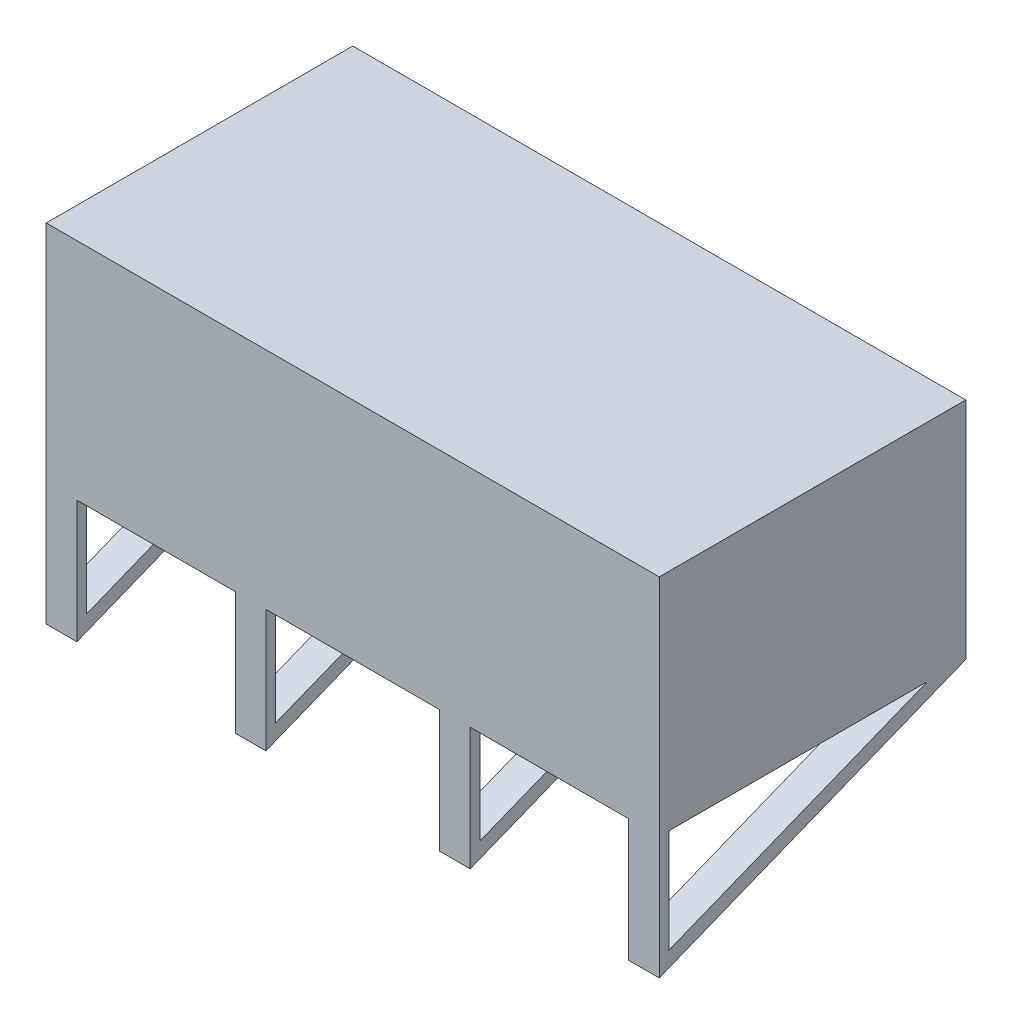
SolidWorks part; units mm, degrees
ref_plane "Front Plane" through (0, 0, 0) normal (0, 0, 1) x (1, 0, 0)
ref_plane "Top Plane" through (0, 0, 0) normal (0, 1, 0) x (1, 0, 0)
ref_plane "Right Plane" through (0, 0, 0) normal (1, 0, 0) x (0, 0, -1)
sketch "LeftSideSketch" plane through (0, 0, 0) normal (1, 0, 0) x (0, 0, -1)
  line L0 (0, 0) -> (150, 0)
  line L1 (150, 0) -> (150, -110)
  line L3 (0, -110) -> (0, 0)
  line L5 (5, -5) -> (5, -105)
  line L6 (5, -105) -> (145, -105)
  line L7 (145, -105) -> (145, -5)
  line L9 (5, -5) -> (145, -5)
  line L10 (0, -110) -> (0, -170)
  line L11 (0, -170) -> (150, -110)
  line L12 (4.8121, -110) -> (4.8121, -160.5359)
  line L13 (4.8121, -160.5359) -> (131.1519, -110)
  line L15 (0, -110) -> (4.8121, -110)
  line L16 (4.8121, -110) -> (131.1519, -110)
  line L17 (131.1519, -110) -> (150, -110)
  dimension "D1" = 150
  dimension "D2" = 110
  dimension "D3" = 5
  dimension "D4" = 5
  dimension "D5" = 5
  dimension "D6" = 5
  dimension "D7" = 7
  dimension "D8" = 4.8121
  dimension "D10" = 60
extrude "Boss-Extrude1" add sketch "LeftSideSketch" along normal blind 300 contours L3 L1 L0 L5 L9 L7 L6 region at (0, -1.8601, -75)
extrude "Boss-Extrude2" add sketch "LeftSideSketch<4>" along normal blind 15 contours L10 L11 L13 L12 region at (0, -111.6155, -2.406)
sketch "LeftSideSketch<4>" plane through (0, 0, 0) normal (1, 0, 0) x (0, 0, -1) same geometry as "LeftSideSketch"
extrude "Boss-Extrude3" add sketch "LeftSideSketch<5>" against normal blind 15 from surface contours L10 L11 L13 L12 region at (0, -111.6155, -2.406) starting at face at (300, -55, -75)
sketch "LeftSideSketch<5>" plane through (0, 0, 0) normal (1, 0, 0) x (0, 0, -1) same geometry as "LeftSideSketch"
ref_plane "refPlane1" through (100, 0, 0) normal (1, 0, 0) x (0, 0, -1)
ref_plane "refPlane2" through (200, 0, 0) normal (1, 0, 0) x (0, 0, -1)
extrude "Boss-Extrude4" add sketch "LeftSideSketch<7>" along normal mid plane 15 from surface contours L17 L13 L12 L15 L10 L11 region at (0, -111.6155, -2.406) starting at plane "refPlane1"
sketch "LeftSideSketch<7>" plane through (0, 0, 0) normal (1, 0, 0) x (0, 0, -1) same geometry as "LeftSideSketch"
extrude "Boss-Extrude5" add sketch "LeftSideSketch<9>" along normal mid plane 15 from surface contours L17 L13 L12 L15 L10 L11 region at (0, -111.6155, -2.406) starting at plane "refPlane2"
sketch "LeftSideSketch<9>" plane through (0, 0, 0) normal (1, 0, 0) x (0, 0, -1) same geometry as "LeftSideSketch"
extrude "Boss-Extrude6" add sketch "LeftSideSketch<10>" along normal blind 5 contours L9 L5 L6 L7 region at (0, -55, -75)
sketch "LeftSideSketch<10>" plane through (0, 0, 0) normal (1, 0, 0) x (0, 0, -1) same geometry as "LeftSideSketch"
extrude "Boss-Extrude7" add sketch "LeftSideSketch<11>" against normal blind 5 from surface contours L9 L5 L6 L7 region at (0, -55, -75) starting at face at (300, -126.8453, -46.9254)
sketch "LeftSideSketch<11>" plane through (0, 0, 0) normal (1, 0, 0) x (0, 0, -1) same geometry as "LeftSideSketch"
sketch "TableSketch" plane through (0, -105, 0) normal (0, 1, 0) x (1, 0, 0)
  line L0 (45, 100) -> (45, 35)
  line L1 (45, 35) -> (205, 35)
  line L2 (205, 35) -> (205, 100)
  line L3 (45, 100) -> (205, 100)
  line L4 (182.75, 100) -> (182.75, 88.75)
  line L5 (182.75, 88.75) -> (195, 88.75)
  line L6 (195, 88.75) -> (195, 46.25)
  line L7 (195, 46.25) -> (152.5, 46.25)
  line L8 (152.5, 46.25) -> (152.5, 88.75)
  line L9 (152.5, 88.75) -> (164.75, 88.75)
  line L10 (164.75, 88.75) -> (164.75, 100)
  line L12 (205, 35) -> (142.5, 35)
  line L13 (205, 35) -> (205, 100)
  line L14 (205, 100) -> (142.5, 100)
  line L15 (142.5, 35) -> (142.5, 100)
  line L16 (295, 5) -> (5, 5) construction
  line L18 (295, 145) -> (295, 5) construction
  circle A0 centre (83.75, 67.5) radius 27
  circle A1 centre (83.75, 67.5) radius 19.2
  circle A3 centre (83.4883, 44.4015) radius 3.9
  circle A4 centre (67.2344, 51.4926) radius 3.9
  circle A5 centre (60.7554, 68) radius 3.9
  circle A6 centre (67.8466, 84.2538) radius 3.9
  circle A7 centre (84.354, 90.7328) radius 3.9
  circle A8 centre (100.6078, 83.6417) radius 3.9
  circle A9 centre (107.0868, 67.1343) radius 3.9
  circle A10 centre (99.9957, 50.8805) radius 3.9
  point P17 (173.75, 67.5)
  point P20 (152.5, 67.5)
  point P41 (0, 0)
  dimension "D7" = 38.4
  dimension "D13" = 54
  dimension "D14" = 8
  dimension "D15" = 90
  dimension "D17" = 32.5
  dimension "D18" = 23
  dimension "D1" = 160
  dimension "D2" = 65
  dimension "D3" = 18
  dimension "D4" = 42.5
  dimension "D5" = 12.25
  dimension "D6" = 11.25
  dimension "D8" = 10
  dimension "D9" = 10
  dimension "D10" = 21.25
  dimension "D11" = 21.25
  dimension "D12" = 90
  dimension "D16" = 30
  dimension "D19" = 33
  dimension "D20" = 23
